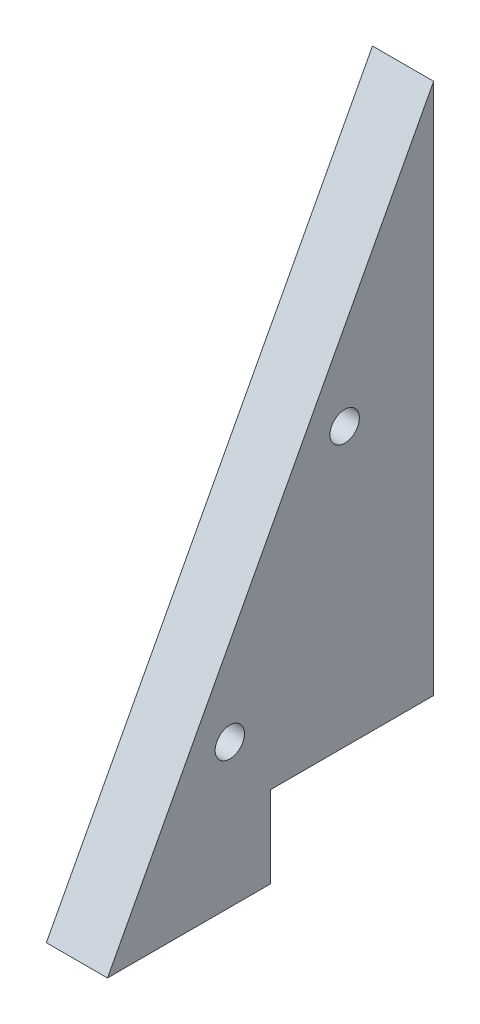
SolidWorks part; units mm, degrees
ref_plane "Front Plane" through (0, 0, 0) normal (0, 0, 1) x (1, 0, 0)
ref_plane "Top Plane" through (0, 0, 0) normal (0, 1, 0) x (1, 0, 0)
ref_plane "Right Plane" through (0, 0, 0) normal (1, 0, 0) x (0, 0, -1)
sketch "Sketch1" plane through (0, 0, 0) normal (1, 0, 0) x (0, 0, -1)
  line L0 (0, 0) -> (-25.4, 0)
  line L1 (-25.4, 0) -> (25.4, 95.5409)
  line L2 (25.4, 95.5409) -> (25.4, 12.7)
  line L3 (25.4, 12.7) -> (0, 12.7)
  line L4 (0, 12.7) -> (0, 0)
  dimension "D1" = 12.7
  dimension "D2" = 25.4
  dimension "62" = 62
  dimension "D4" = 25.4
extrude "Boss-Extrude1" add sketch "Sketch1" along normal blind 9.525
sketch "Sketch2" plane through (0, 12.7, 0) normal (0, -1, 0) x (1, 0, 0)
  line L0 (0, 0) -> (0, -25.4) construction
  line L1 (9.525, -25.4) -> (0, -25.4) construction
  circle A1 centre (4.7625, -19.05) radius 1.905
  circle A2 centre (4.7625, -6.35) radius 1.905
  dimension "D2" = 3.81
  dimension "D3" = 6.35
  dimension "D1" = 4.7625
  dimension "D4" = 2
extrude "Cut-Extrude1" cut sketch "Sketch2" against normal blind 9.525
sketch "Sketch3" plane through (9.525, 0, 0) normal (1, 0, 0) x (0, 0, -1)
  line L0 (11.5369, 55.9423) -> (-6.35, 22.302) construction
  line L2 (25.4, 95.5409) -> (-25.4, 0) construction
  line L3 (0, 0) -> (0, 12.7) construction
  circle A0 centre (-6.35, 22.302) radius 2.286
  circle A1 centre (11.5369, 55.9423) radius 2.286
  dimension "D3" = 4.572
  dimension "D4" = 6.35
  dimension "D1" = 38.1
  dimension "D2" = 6.35
extrude "Cut-Extrude2" cut sketch "Sketch3" against normal through all
